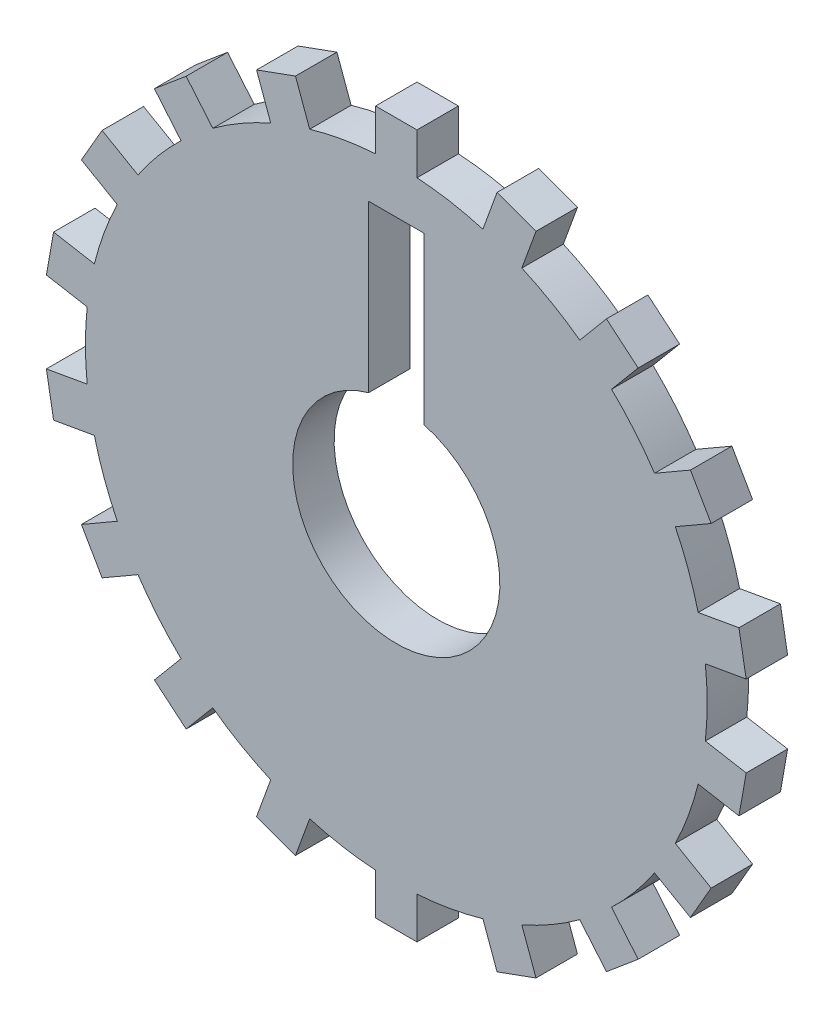
SolidWorks part; units mm, degrees
ref_plane "Front Plane" through (0, 0, 0) normal (0, 0, 1) x (1, 0, 0)
ref_plane "Top Plane" through (0, 0, 0) normal (0, 1, 0) x (1, 0, 0)
ref_plane "Right Plane" through (0, 0, 0) normal (1, 0, 0) x (0, 0, -1)
sketch "Sketch1" plane through (0, 0, 0) normal (0, 0, 1) x (1, 0, 0)
  line L0 (0, 0) -> (0, 22.5) construction
  line L1 (-1.5, 22.4499) -> (-1.5, 25.4499)
  line L2 (-1.5, 25.4499) -> (1.5, 25.4499)
  line L3 (1.5, 22.4499) -> (1.5, 25.4499)
  line L4 (-2, 7.2284) -> (-2, 19.2284)
  line L5 (-2, 19.2284) -> (2, 19.2284)
  line L6 (2, 7.2284) -> (2, 19.2284)
  circle A0 centre (0, 0) radius 22.5
  circle A1 centre (0, 0) radius 7.5
  point P8 (0, 25.4499)
  point P15 (0, 15.6071)
  point P16 (0, 19.2284)
  dimension "D2" = 45
  dimension "D4" = 15
  dimension "D1" = 3
  dimension "D3" = 3
  dimension "D5" = 4
  dimension "D6" = 12
extrude "Boss-Extrude1" add sketch "Sketch1" along normal mid plane 3 contours A0 region at (0, 21.8636, 0)
extrude "Boss-Extrude2" add sketch "Sketch1<3>" along normal mid plane 3 contours A0 L3 L2 L1 region at (0, 23.9666, 0)
sketch "Sketch1<3>" plane through (0, 0, 0) normal (0, 0, 1) x (1, 0, 0) same geometry as "Sketch1"
ref_axis "Axis1" through (0, 0, 13.2194) along (0, 0, -1)
pattern_circular "CirPattern1" count 18 over 360 about axis through (0, 0, 13.2194) along (0, 0, -1) of "Boss-Extrude2"
